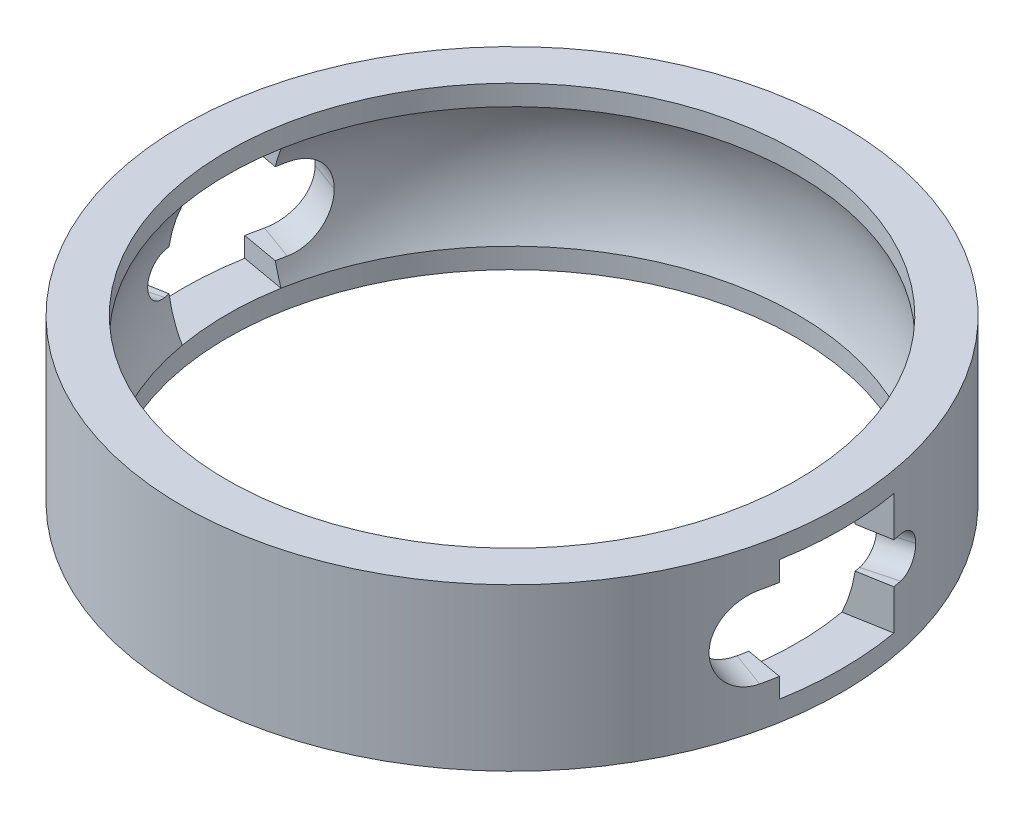
SolidWorks part; units mm, degrees
material "Nylon 101"
ref_plane "Front Plane" through (0, 0, 0) normal (0, 0, 1) x (1, 0, 0)
ref_plane "Top Plane" through (0, 0, 0) normal (0, 1, 0) x (1, 0, 0)
ref_plane "Right Plane" through (0, 0, 0) normal (1, 0, 0) x (0, 0, -1)
sketch "Sketch1" plane through (0, 0, 0) normal (0, 0, 1) x (1, 0, 0)
  line L0 (0, 0) -> (0, 12.3745) construction
  line L1 (-17.78, 0) -> (0, 0) construction
  line L2 (-20.574, 5.0419) -> (-17.78, 5.0419)
  line L3 (-20.574, 5.0419) -> (-20.574, -5.0419)
  line L4 (-20.574, -5.0419) -> (-17.78, -5.0419)
  line L5 (-17.78, 5.0419) -> (-17.78, -5.0419)
  dimension "D1" = 35.56
  dimension "D2" = 2.794
  dimension "D3" = 10.0838
revolve "Revolve1" add sketch "Sketch1" angle 360 about L0
sketch "Sketch2" plane through (0, 0, 0) normal (0, 0, 1) x (1, 0, 0)
  line L0 (-17.78, 5.0419) -> (-17.78, -5.0419) construction
  line L1 (-17.78, 0) -> (-18.5737, 0) construction
  line L2 (-17.78, 3.7719) -> (-15.24, 3.7719)
  line L3 (-15.24, 3.7719) -> (-15.24, -3.7719)
  line L4 (-15.24, -3.7719) -> (-17.78, -3.7719)
  line L5 (-17.78, 3.7719) -> (-17.78, 5.0419) construction
  arc A0 (-17.78, 3.7719) -> (-17.78, -3.7719) centre (-9.2148, 0) ccw
  dimension "D1" = 0.7937
  dimension "D2" = 1.27
  dimension "D3" = 2.54
revolve "Cut-Revolve1" cut sketch "Sketch2" angle 360 about L0
sketch "Sketch4" plane through (0, 0, 0) normal (0, 0, 1) x (1, 0, 0)
  line L1 (-1.27, 3.7592) -> (-1.27, -3.7592)
  line L2 (-1.27, 3.7592) -> (0, 3.7592)
  line L3 (0, 3.7592) -> (0, -3.7592) construction
  line L4 (0, -3.7592) -> (-1.27, -3.7592)
  arc A0 (0, -3.7592) -> (0, 3.7592) centre (0, 0) ccw
  dimension "D2" = 7.5184
  dimension "D1" = 1.27
extrude "Cut-Extrude1" [suppressed] cut sketch "Sketch4" against normal through all
sketch "Sketch5" [suppressed] plane through (0, 0, 0) normal (0, 1, 0) x (1, 0, 0)
  line L0 (0, 0) -> (0, 20.574) construction
  line L1 (0, 0) -> (20.574, 0) construction
  line L2 (0, 0) -> (7.0367, -19.3332) construction
  line L3 (12.5813, -17.3152) -> (1.4922, -21.3513) construction
  circle A0 centre (0, 0) radius 20.574 construction
  dimension "D1" = 160
ref_plane "Plane1" [suppressed] through (7.0367, 0, 19.3332) normal (0.342, 0, 0.9397) x (0.9397, 0, -0.342)
sketch "Sketch6" [suppressed] plane through (7.0367, 0, 19.3332) normal (0.342, 0, 0.9397) x (0.9397, 0, -0.342)
  line L0 (1.27, 3.7592) -> (0, 3.7592)
  line L1 (1.27, 3.7592) -> (1.27, 1.2531)
  line L2 (1.27, -1.2531) -> (1.27, -3.7592)
  line L3 (0, 3.7592) -> (0, -3.7592)
  line L4 (0, -3.7592) -> (1.27, -3.7592)
  line L5 (1.27, 0) -> (0, 0) construction
  arc A0 (1.27, 1.2531) -> (1.27, -1.2531) centre (1.27, 0) cw
  point P11 (0, 0)
  dimension "D3" = 1.2531
  dimension "D1" = 1.27
  dimension "D2" = 7.5184
extrude "Cut-Extrude2" [suppressed] cut sketch "Sketch6" against normal up to surface (2.1282 mm away) up to face at (0, -3.7719, -17.78)
pattern_circular "CirPattern1" [suppressed] count 2 over 360 of bodies 104
sketch "Sketch7" plane through (0, 0, 0) normal (0, 0, 1) x (1, 0, 0)
  line L1 (-27.94, 3.7719) -> (-17.78, 3.7719)
  line L2 (-27.94, 3.7719) -> (-27.94, -3.7719)
  line L3 (-27.94, -3.7719) -> (-17.78, -3.7719)
  line L4 (-17.78, 3.7719) -> (-17.78, -3.7719)
  line L8 (0, 0) -> (0, 11.6555) construction
  dimension "D1" = 10.16
revolve "Cut-Revolve2" cut sketch "Sketch7" angle 20 mid plane about L8
sketch "Sketch8" plane through (0, 0, 0) normal (-0.1736, 0, 0.9848) x (0.9848, 0, 0.1736)
  line L0 (-18.2225, 0) -> (0, 0) construction
  line L1 (-28.3825, 2.54) -> (-18.2225, 2.54)
  line L2 (-28.3825, 2.54) -> (-28.3825, -2.54)
  line L3 (-28.3825, -2.54) -> (-18.2225, -2.54)
  line L4 (-18.2225, 2.54) -> (-18.2225, -2.54)
  line L5 (0, 0) -> (0, 12.0795) construction
  arc A0 (-17.78, 3.7719) -> (-17.78, -3.7719) centre (-9.2148, 0) ccw construction
  dimension "D1" = 5.08
  dimension "D2" = 10.16
revolve "Cut-Revolve3" cut sketch "Sketch8" angle 10 about L5 reverse direction yes
sketch "Sketch9" plane through (0, 0, 0) normal (-0.1736, 0, -0.9848) x (-0.9848, 0, 0.1736)
  line L0 (18.4872, 0) -> (0, 0) construction
  line L1 (18.4872, 1.27) -> (28.6472, 1.27)
  line L2 (18.4872, 1.27) -> (18.4872, -1.27)
  line L3 (18.4872, -1.27) -> (28.6472, -1.27)
  line L4 (28.6472, 1.27) -> (28.6472, -1.27)
  line L5 (0, 0) -> (0, 12.4005) construction
  arc A0 (17.78, -3.7719) -> (17.78, 3.7719) centre (9.2148, 0) ccw construction
  dimension "D1" = 2.54
  dimension "D2" = 10.16
revolve "Cut-Revolve4" cut sketch "Sketch9" angle 5 about L5
pattern_circular "CirPattern2" count 2 over 360 about axis through (0, 0, 0) along (0, -1, 0) of "Cut-Revolve2", "Cut-Revolve3", "Cut-Revolve4"
fillet "Fillet1" radius 2.54 4 edges at (18.2284, 2.54, 6.6346) (18.2284, -2.54, 6.6346) (-18.2284, -2.54, -6.6346) (-18.2284, 2.54, -6.6346)
fillet "Fillet2" radius 1.27 4 edges at (-18.8651, -1.27, 5.0549) (-18.8651, 1.27, 5.0549) (18.8651, -1.27, -5.0549) (18.8651, 1.27, -5.0549)
equation "\"D3@Sketch6\"=\"D2@Sketch6\"/2/3"
